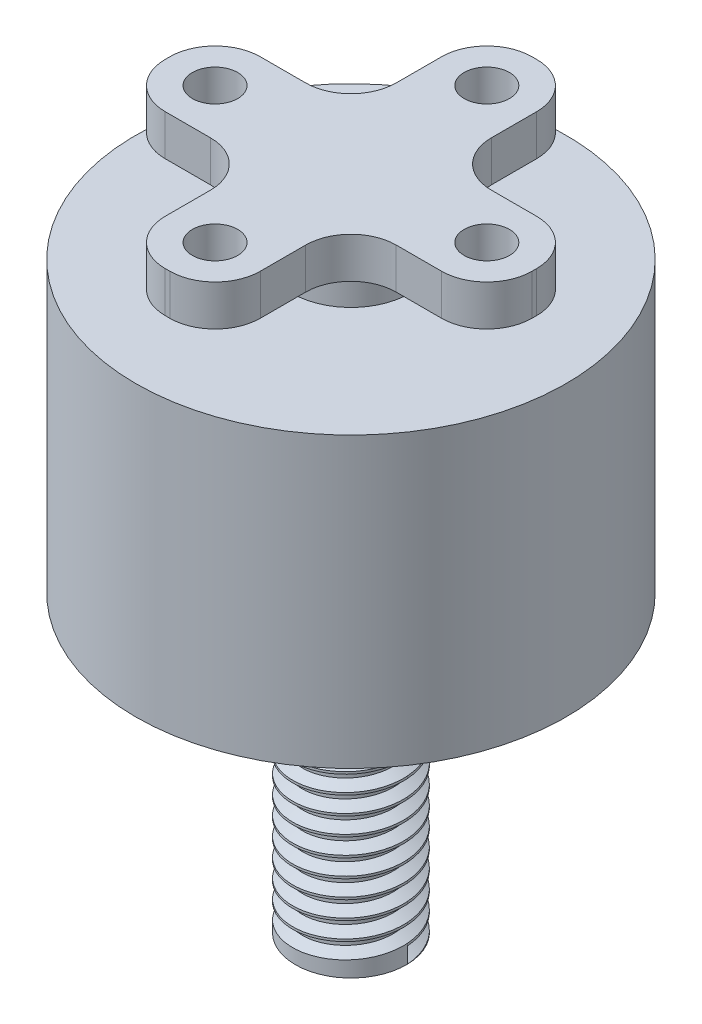
SolidWorks part; units mm, degrees
ref_plane "Ebene vorne" through (0, 0, 0) normal (0, 0, 1) x (1, 0, 0)
ref_plane "Ebene oben" through (0, 0, 0) normal (0, 1, 0) x (1, 0, 0)
ref_plane "Ebene rechts" through (0, 0, 0) normal (1, 0, 0) x (0, 0, -1)
sketch "Skizze1" plane through (0, 0, 0) normal (0, 1, 0) x (1, 0, 0)
  circle A0 centre (0, 0) radius 2.45
  dimension "D1" = 4.9
extrude "Aufsatz-Linear austragen1" add sketch "Skizze1" along normal blind 13
thread "Gewinde1" pitch 0.8 method cut profile "Gewindeprofil1" start angle 1, offset 0, length 0, pitch 0.8, diameter 4.9
ref_plane "Ebene1" through (2.4496, 0, -0.0428) normal (0.0175, 0, 0.9998) x (0.9998, 0, -0.0175)
sketch "Gewindeprofil1" plane through (2.4496, 0, -0.0428) normal (0.0175, 0, 0.9998) x (0.9998, 0, -0.0175)
  line L0 (0, 0) -> (0, 0.8) construction
  line L11 (0, 0) -> (0, 0.7)
  line L12 (0, 0.7) -> (-0.433, 0.45)
  line L13 (-0.433, 0.45) -> (-0.433, 0.25)
  line L15 (-0.433, 0.25) -> (0, 0)
  line L17 (-0.433, 0.35) -> (0, 0.35) construction
  point P2 (0, 0)
  dimension "Pitch" = 0.8
  dimension "Profile_Angle" = 60
  dimension "Profile_Land" = 0.2
  dimension "Profile_Height" = 0.433
sketch "Skizze11" plane through (0, 13, 0) normal (0, 1, 0) x (1, 0, 0)
  circle A0 centre (0, 0) radius 9.5
  dimension "D1" = 19
extrude "Aufsatz-Linear austragen2" add sketch "Skizze11" along normal blind 12.75
sketch "Skizze12" plane through (0, 25.75, 0) normal (0, 1, 0) x (1, 0, 0)
  circle A0 centre (0, 0) radius 2.6
  dimension "D1" = 5.2
extrude "Aufsatz-Linear austragen3" add sketch "Skizze12" along normal blind 1.85
sketch "Skizze13" plane through (0, 27.6, 0) normal (0, 1, 0) x (1, 0, 0)
  line L0 (-2.1, 8.1) -> (2.1, 8.1)
  line L1 (2.1, 8.1) -> (2.1, 2.1)
  line L2 (2.1, 2.1) -> (8.1, 2.1)
  line L3 (8.1, 2.1) -> (8.1, -2.1)
  line L4 (8.1, -2.1) -> (2.1, -2.1)
  line L5 (2.1, -2.1) -> (2.1, -8.1)
  line L6 (2.1, -8.1) -> (-2.1, -8.1)
  line L7 (-2.1, -8.1) -> (-2.1, -2.1)
  line L8 (-2.1, -2.1) -> (-8.1, -2.1)
  line L9 (-8.1, -2.1) -> (-8.1, 2.1)
  line L10 (-8.1, 2.1) -> (-2.1, 2.1)
  line L11 (-2.1, 2.1) -> (-2.1, 8.1)
  line L12 (0, 13.3131) -> (0, -13.4486) construction
  line L13 (-14.9669, 0) -> (13.6254, 0) construction
  dimension "D1" = 6
  dimension "D2" = 6
  dimension "D3" = 6
  dimension "D4" = 6
  dimension "D5" = 4.2
  dimension "D6" = 4.2
extrude "Aufsatz-Linear austragen4" add sketch "Skizze13" along normal blind 1.8
fillet "Verrundung1" radius 2 12 edges at (2.1, 28.5, -2.1) (2.1, 28.5, 2.1) (-2.1, 28.5, 2.1) (-2.1, 28.5, -2.1) (-8.1, 28.5, -2.1) (-8.1, 28.5, 2.1) (-2.1, 28.5, 8.1) (2.1, 28.5, 8.1) (8.1, 28.5, 2.1) (8.1, 28.5, -2.1) (-2.1, 28.5, -8.1) (2.1, 28.5, -8.1)
sketch "Skizze14" plane through (0, 29.4, 0) normal (0, 1, 0) x (1, 0, 0)
  line L0 (14.4677, 0) -> (-14.2716, 0) construction
  line L1 (0, -11.3115) -> (0, 10.2921) construction
  circle A0 centre (0, 0) radius 6 construction
  circle A1 centre (-6, 0) radius 1
  circle A2 centre (0, 6) radius 1
  circle A3 centre (6, 0) radius 1
  circle A4 centre (0, -6) radius 1
  point P18 (0, 0)
  dimension "D1" = 12
  dimension "D2" = 2
  dimension "D3" = 4
extrude "Schnitt-Linear austragen5" cut sketch "Skizze14" against normal up to surface (1.8 mm away) up to face at (0, 27.6, 2.6)
